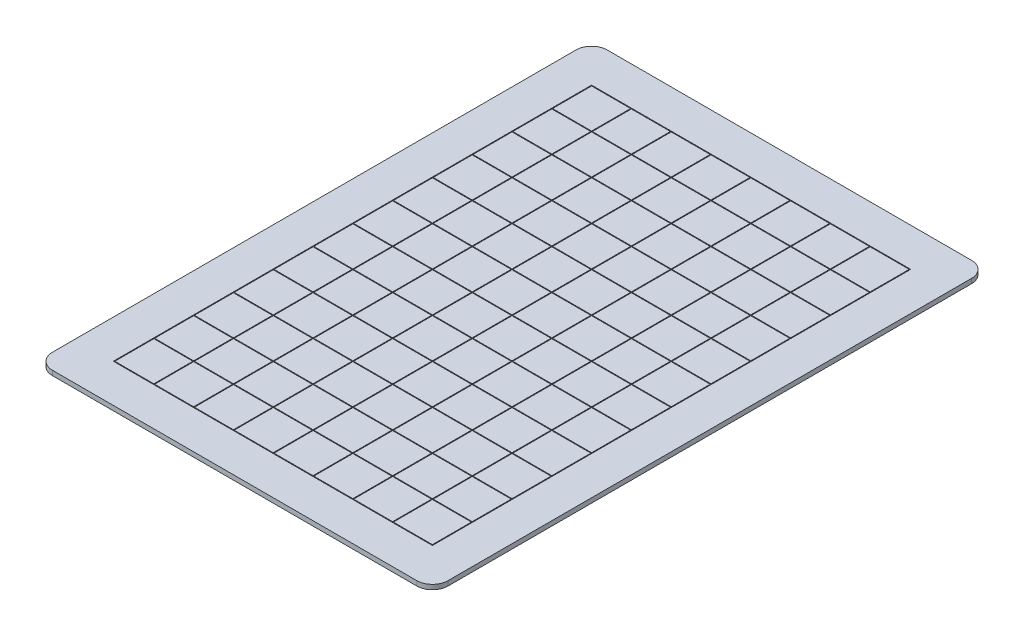
SolidWorks part; units mm, degrees
ref_plane "Front Plane" through (0, 0, 0) normal (0, 0, 1) x (1, 0, 0)
ref_plane "Top Plane" through (0, 0, 0) normal (0, 1, 0) x (1, 0, 0)
ref_plane "Right Plane" through (0, 0, 0) normal (1, 0, 0) x (0, 0, -1)
sketch "Sketch1" plane through (0, 0, 0) normal (0, 1, 0) x (1, 0, 0)
  line L1 (0, 0) -> (253.5, 0)
  line L2 (0, 0) -> (0, 355.5)
  line L3 (0, 355.5) -> (253.5, 355.5)
  line L4 (253.5, 0) -> (253.5, 355.5)
  dimension "D1" = 253.5
  dimension "D2" = 355.5
extrude "Boss-Extrude1" add sketch "Sketch1" along normal blind 3
sketch "Sketch2" plane through (0, 3, 0) normal (0, 1, 0) x (1, 0, 0)
  line L0 (0, 0) -> (253.5, 0) construction
  line L1 (25, 50) -> (50, 50)
  line L2 (25, 50) -> (25, 25)
  line L3 (25, 25) -> (50, 25)
  line L4 (50, 50) -> (50, 25)
  line L5 (0, 355.5) -> (0, 0) construction
  line L6 (50.5, 50) -> (50.5, 25)
  line L7 (50.5, 50) -> (75.5, 50)
  line L8 (75.5, 50) -> (75.5, 25)
  line L9 (50.5, 25) -> (75.5, 25)
  line L10 (76, 50) -> (76, 25)
  line L11 (76, 50) -> (101, 50)
  line L12 (101, 50) -> (101, 25)
  line L13 (76, 25) -> (101, 25)
  line L14 (101.5, 50) -> (101.5, 25)
  line L15 (101.5, 50) -> (126.5, 50)
  line L16 (126.5, 50) -> (126.5, 25)
  line L17 (101.5, 25) -> (126.5, 25)
  line L18 (127, 50) -> (127, 25)
  line L19 (127, 50) -> (152, 50)
  line L20 (152, 50) -> (152, 25)
  line L21 (127, 25) -> (152, 25)
  line L22 (152.5, 50) -> (152.5, 25)
  line L23 (152.5, 50) -> (177.5, 50)
  line L24 (177.5, 50) -> (177.5, 25)
  line L25 (152.5, 25) -> (177.5, 25)
  line L26 (178, 50) -> (178, 25)
  line L27 (178, 50) -> (203, 50)
  line L28 (203, 50) -> (203, 25)
  line L29 (178, 25) -> (203, 25)
  line L30 (203.5, 50) -> (203.5, 25)
  line L31 (203.5, 50) -> (228.5, 50)
  line L32 (228.5, 50) -> (228.5, 25)
  line L33 (203.5, 25) -> (228.5, 25)
  line L34 (50.5, 75.5) -> (50.5, 50.5)
  line L35 (50.5, 75.5) -> (75.5, 75.5)
  line L36 (75.5, 75.5) -> (75.5, 50.5)
  line L37 (50.5, 50.5) -> (75.5, 50.5)
  line L38 (76, 75.5) -> (76, 50.5)
  line L39 (76, 75.5) -> (101, 75.5)
  line L40 (101, 75.5) -> (101, 50.5)
  line L41 (76, 50.5) -> (101, 50.5)
  line L42 (101.5, 75.5) -> (101.5, 50.5)
  line L43 (101.5, 75.5) -> (126.5, 75.5)
  line L44 (126.5, 75.5) -> (126.5, 50.5)
  line L45 (101.5, 50.5) -> (126.5, 50.5)
  line L46 (127, 75.5) -> (127, 50.5)
  line L47 (127, 75.5) -> (152, 75.5)
  line L48 (152, 75.5) -> (152, 50.5)
  line L49 (127, 50.5) -> (152, 50.5)
  line L50 (152.5, 75.5) -> (152.5, 50.5)
  line L51 (152.5, 75.5) -> (177.5, 75.5)
  line L52 (177.5, 75.5) -> (177.5, 50.5)
  line L53 (152.5, 50.5) -> (177.5, 50.5)
  line L54 (178, 75.5) -> (178, 50.5)
  line L55 (178, 75.5) -> (203, 75.5)
  line L56 (203, 75.5) -> (203, 50.5)
  line L57 (178, 50.5) -> (203, 50.5)
  line L58 (203.5, 75.5) -> (203.5, 50.5)
  line L59 (203.5, 75.5) -> (228.5, 75.5)
  line L60 (228.5, 75.5) -> (228.5, 50.5)
  line L61 (203.5, 50.5) -> (228.5, 50.5)
  line L62 (50.5, 101) -> (50.5, 76)
  line L63 (50.5, 101) -> (75.5, 101)
  line L64 (75.5, 101) -> (75.5, 76)
  line L65 (50.5, 76) -> (75.5, 76)
  line L66 (76, 101) -> (76, 76)
  line L67 (76, 101) -> (101, 101)
  line L68 (101, 101) -> (101, 76)
  line L69 (76, 76) -> (101, 76)
  line L70 (101.5, 101) -> (101.5, 76)
  line L71 (101.5, 101) -> (126.5, 101)
  line L72 (126.5, 101) -> (126.5, 76)
  line L73 (101.5, 76) -> (126.5, 76)
  line L74 (127, 101) -> (127, 76)
  line L75 (127, 101) -> (152, 101)
  line L76 (152, 101) -> (152, 76)
  line L77 (127, 76) -> (152, 76)
  line L78 (152.5, 101) -> (152.5, 76)
  line L79 (152.5, 101) -> (177.5, 101)
  line L80 (177.5, 101) -> (177.5, 76)
  line L81 (152.5, 76) -> (177.5, 76)
  line L82 (178, 101) -> (178, 76)
  line L83 (178, 101) -> (203, 101)
  line L84 (203, 101) -> (203, 76)
  line L85 (178, 76) -> (203, 76)
  line L86 (203.5, 101) -> (203.5, 76)
  line L87 (203.5, 101) -> (228.5, 101)
  line L88 (228.5, 101) -> (228.5, 76)
  line L89 (203.5, 76) -> (228.5, 76)
  line L90 (50.5, 126.5) -> (50.5, 101.5)
  line L91 (50.5, 126.5) -> (75.5, 126.5)
  line L92 (75.5, 126.5) -> (75.5, 101.5)
  line L93 (50.5, 101.5) -> (75.5, 101.5)
  line L94 (76, 126.5) -> (76, 101.5)
  line L95 (76, 126.5) -> (101, 126.5)
  line L96 (101, 126.5) -> (101, 101.5)
  line L97 (76, 101.5) -> (101, 101.5)
  line L98 (101.5, 126.5) -> (101.5, 101.5)
  line L99 (101.5, 126.5) -> (126.5, 126.5)
  line L100 (126.5, 126.5) -> (126.5, 101.5)
  line L101 (101.5, 101.5) -> (126.5, 101.5)
  line L102 (127, 126.5) -> (127, 101.5)
  line L103 (127, 126.5) -> (152, 126.5)
  line L104 (152, 126.5) -> (152, 101.5)
  line L105 (127, 101.5) -> (152, 101.5)
  line L106 (152.5, 126.5) -> (152.5, 101.5)
  line L107 (152.5, 126.5) -> (177.5, 126.5)
  line L108 (177.5, 126.5) -> (177.5, 101.5)
  line L109 (152.5, 101.5) -> (177.5, 101.5)
  line L110 (178, 126.5) -> (178, 101.5)
  line L111 (178, 126.5) -> (203, 126.5)
  line L112 (203, 126.5) -> (203, 101.5)
  line L113 (178, 101.5) -> (203, 101.5)
  line L114 (203.5, 126.5) -> (203.5, 101.5)
  line L115 (203.5, 126.5) -> (228.5, 126.5)
  line L116 (228.5, 126.5) -> (228.5, 101.5)
  line L117 (203.5, 101.5) -> (228.5, 101.5)
  line L118 (50.5, 152) -> (50.5, 127)
  line L119 (50.5, 152) -> (75.5, 152)
  line L120 (75.5, 152) -> (75.5, 127)
  line L121 (50.5, 127) -> (75.5, 127)
  line L122 (76, 152) -> (76, 127)
  line L123 (76, 152) -> (101, 152)
  line L124 (101, 152) -> (101, 127)
  line L125 (76, 127) -> (101, 127)
  line L126 (101.5, 152) -> (101.5, 127)
  line L127 (101.5, 152) -> (126.5, 152)
  line L128 (126.5, 152) -> (126.5, 127)
  line L129 (101.5, 127) -> (126.5, 127)
  line L130 (127, 152) -> (127, 127)
  line L131 (127, 152) -> (152, 152)
  line L132 (152, 152) -> (152, 127)
  line L133 (127, 127) -> (152, 127)
  line L134 (152.5, 152) -> (152.5, 127)
  line L135 (152.5, 152) -> (177.5, 152)
  line L136 (177.5, 152) -> (177.5, 127)
  line L137 (152.5, 127) -> (177.5, 127)
  line L138 (178, 152) -> (178, 127)
  line L139 (178, 152) -> (203, 152)
  line L140 (203, 152) -> (203, 127)
  line L141 (178, 127) -> (203, 127)
  line L142 (203.5, 152) -> (203.5, 127)
  line L143 (203.5, 152) -> (228.5, 152)
  line L144 (228.5, 152) -> (228.5, 127)
  line L145 (203.5, 127) -> (228.5, 127)
  line L146 (50.5, 177.5) -> (50.5, 152.5)
  line L147 (50.5, 177.5) -> (75.5, 177.5)
  line L148 (75.5, 177.5) -> (75.5, 152.5)
  line L149 (50.5, 152.5) -> (75.5, 152.5)
  line L150 (76, 177.5) -> (76, 152.5)
  line L151 (76, 177.5) -> (101, 177.5)
  line L152 (101, 177.5) -> (101, 152.5)
  line L153 (76, 152.5) -> (101, 152.5)
  line L154 (101.5, 177.5) -> (101.5, 152.5)
  line L155 (101.5, 177.5) -> (126.5, 177.5)
  line L156 (126.5, 177.5) -> (126.5, 152.5)
  line L157 (101.5, 152.5) -> (126.5, 152.5)
  line L158 (127, 177.5) -> (127, 152.5)
  line L159 (127, 177.5) -> (152, 177.5)
  line L160 (152, 177.5) -> (152, 152.5)
  line L161 (127, 152.5) -> (152, 152.5)
  line L162 (152.5, 177.5) -> (152.5, 152.5)
  line L163 (152.5, 177.5) -> (177.5, 177.5)
  line L164 (177.5, 177.5) -> (177.5, 152.5)
  line L165 (152.5, 152.5) -> (177.5, 152.5)
  line L166 (178, 177.5) -> (178, 152.5)
  line L167 (178, 177.5) -> (203, 177.5)
  line L168 (203, 177.5) -> (203, 152.5)
  line L169 (178, 152.5) -> (203, 152.5)
  line L170 (203.5, 177.5) -> (203.5, 152.5)
  line L171 (203.5, 177.5) -> (228.5, 177.5)
  line L172 (228.5, 177.5) -> (228.5, 152.5)
  line L173 (203.5, 152.5) -> (228.5, 152.5)
  line L174 (50.5, 203) -> (50.5, 178)
  line L175 (50.5, 203) -> (75.5, 203)
  line L176 (75.5, 203) -> (75.5, 178)
  line L177 (50.5, 178) -> (75.5, 178)
  line L178 (76, 203) -> (76, 178)
  line L179 (76, 203) -> (101, 203)
  line L180 (101, 203) -> (101, 178)
  line L181 (76, 178) -> (101, 178)
  line L182 (101.5, 203) -> (101.5, 178)
  line L183 (101.5, 203) -> (126.5, 203)
  line L184 (126.5, 203) -> (126.5, 178)
  line L185 (101.5, 178) -> (126.5, 178)
  line L186 (127, 203) -> (127, 178)
  line L187 (127, 203) -> (152, 203)
  line L188 (152, 203) -> (152, 178)
  line L189 (127, 178) -> (152, 178)
  line L190 (152.5, 203) -> (152.5, 178)
  line L191 (152.5, 203) -> (177.5, 203)
  line L192 (177.5, 203) -> (177.5, 178)
  line L193 (152.5, 178) -> (177.5, 178)
  line L194 (178, 203) -> (178, 178)
  line L195 (178, 203) -> (203, 203)
  line L196 (203, 203) -> (203, 178)
  line L197 (178, 178) -> (203, 178)
  line L198 (203.5, 203) -> (203.5, 178)
  line L199 (203.5, 203) -> (228.5, 203)
  line L200 (228.5, 203) -> (228.5, 178)
  line L201 (203.5, 178) -> (228.5, 178)
  line L202 (50.5, 228.5) -> (50.5, 203.5)
  line L203 (50.5, 228.5) -> (75.5, 228.5)
  line L204 (75.5, 228.5) -> (75.5, 203.5)
  line L205 (50.5, 203.5) -> (75.5, 203.5)
  line L206 (76, 228.5) -> (76, 203.5)
  line L207 (76, 228.5) -> (101, 228.5)
  line L208 (101, 228.5) -> (101, 203.5)
  line L209 (76, 203.5) -> (101, 203.5)
  line L210 (101.5, 228.5) -> (101.5, 203.5)
  line L211 (101.5, 228.5) -> (126.5, 228.5)
  line L212 (126.5, 228.5) -> (126.5, 203.5)
  line L213 (101.5, 203.5) -> (126.5, 203.5)
  line L214 (127, 228.5) -> (127, 203.5)
  line L215 (127, 228.5) -> (152, 228.5)
  line L216 (152, 228.5) -> (152, 203.5)
  line L217 (127, 203.5) -> (152, 203.5)
  line L218 (152.5, 228.5) -> (152.5, 203.5)
  line L219 (152.5, 228.5) -> (177.5, 228.5)
  line L220 (177.5, 228.5) -> (177.5, 203.5)
  line L221 (152.5, 203.5) -> (177.5, 203.5)
  line L222 (178, 228.5) -> (178, 203.5)
  line L223 (178, 228.5) -> (203, 228.5)
  line L224 (203, 228.5) -> (203, 203.5)
  line L225 (178, 203.5) -> (203, 203.5)
  line L226 (203.5, 228.5) -> (203.5, 203.5)
  line L227 (203.5, 228.5) -> (228.5, 228.5)
  line L228 (228.5, 228.5) -> (228.5, 203.5)
  line L229 (203.5, 203.5) -> (228.5, 203.5)
  line L230 (50.5, 254) -> (50.5, 229)
  line L231 (50.5, 254) -> (75.5, 254)
  line L232 (75.5, 254) -> (75.5, 229)
  line L233 (50.5, 229) -> (75.5, 229)
  line L234 (76, 254) -> (76, 229)
  line L235 (76, 254) -> (101, 254)
  line L236 (101, 254) -> (101, 229)
  line L237 (76, 229) -> (101, 229)
  line L238 (101.5, 254) -> (101.5, 229)
  line L239 (101.5, 254) -> (126.5, 254)
  line L240 (126.5, 254) -> (126.5, 229)
  line L241 (101.5, 229) -> (126.5, 229)
  line L242 (127, 254) -> (127, 229)
  line L243 (127, 254) -> (152, 254)
  line L244 (152, 254) -> (152, 229)
  line L245 (127, 229) -> (152, 229)
  line L246 (152.5, 254) -> (152.5, 229)
  line L247 (152.5, 254) -> (177.5, 254)
  line L248 (177.5, 254) -> (177.5, 229)
  line L249 (152.5, 229) -> (177.5, 229)
  line L250 (178, 254) -> (178, 229)
  line L251 (178, 254) -> (203, 254)
  line L252 (203, 254) -> (203, 229)
  line L253 (178, 229) -> (203, 229)
  line L254 (203.5, 254) -> (203.5, 229)
  line L255 (203.5, 254) -> (228.5, 254)
  line L256 (228.5, 254) -> (228.5, 229)
  line L257 (203.5, 229) -> (228.5, 229)
  line L258 (50.5, 279.5) -> (50.5, 254.5)
  line L259 (50.5, 279.5) -> (75.5, 279.5)
  line L260 (75.5, 279.5) -> (75.5, 254.5)
  line L261 (50.5, 254.5) -> (75.5, 254.5)
  line L262 (76, 279.5) -> (76, 254.5)
  line L263 (76, 279.5) -> (101, 279.5)
  line L264 (101, 279.5) -> (101, 254.5)
  line L265 (76, 254.5) -> (101, 254.5)
  line L266 (101.5, 279.5) -> (101.5, 254.5)
  line L267 (101.5, 279.5) -> (126.5, 279.5)
  line L268 (126.5, 279.5) -> (126.5, 254.5)
  line L269 (101.5, 254.5) -> (126.5, 254.5)
  line L270 (127, 279.5) -> (127, 254.5)
  line L271 (127, 279.5) -> (152, 279.5)
  line L272 (152, 279.5) -> (152, 254.5)
  line L273 (127, 254.5) -> (152, 254.5)
  line L274 (152.5, 279.5) -> (152.5, 254.5)
  line L275 (152.5, 279.5) -> (177.5, 279.5)
  line L276 (177.5, 279.5) -> (177.5, 254.5)
  line L277 (152.5, 254.5) -> (177.5, 254.5)
  line L278 (178, 279.5) -> (178, 254.5)
  line L279 (178, 279.5) -> (203, 279.5)
  line L280 (203, 279.5) -> (203, 254.5)
  line L281 (178, 254.5) -> (203, 254.5)
  line L282 (203.5, 279.5) -> (203.5, 254.5)
  line L283 (203.5, 279.5) -> (228.5, 279.5)
  line L284 (228.5, 279.5) -> (228.5, 254.5)
  line L285 (203.5, 254.5) -> (228.5, 254.5)
  line L286 (50.5, 305) -> (50.5, 280)
  line L287 (50.5, 305) -> (75.5, 305)
  line L288 (75.5, 305) -> (75.5, 280)
  line L289 (50.5, 280) -> (75.5, 280)
  line L290 (76, 305) -> (76, 280)
  line L291 (76, 305) -> (101, 305)
  line L292 (101, 305) -> (101, 280)
  line L293 (76, 280) -> (101, 280)
  line L294 (101.5, 305) -> (101.5, 280)
  line L295 (101.5, 305) -> (126.5, 305)
  line L296 (126.5, 305) -> (126.5, 280)
  line L297 (101.5, 280) -> (126.5, 280)
  line L298 (127, 305) -> (127, 280)
  line L299 (127, 305) -> (152, 305)
  line L300 (152, 305) -> (152, 280)
  line L301 (127, 280) -> (152, 280)
  line L302 (152.5, 305) -> (152.5, 280)
  line L303 (152.5, 305) -> (177.5, 305)
  line L304 (177.5, 305) -> (177.5, 280)
  line L305 (152.5, 280) -> (177.5, 280)
  line L306 (178, 305) -> (178, 280)
  line L307 (178, 305) -> (203, 305)
  line L308 (203, 305) -> (203, 280)
  line L309 (178, 280) -> (203, 280)
  line L310 (203.5, 305) -> (203.5, 280)
  line L311 (203.5, 305) -> (228.5, 305)
  line L312 (228.5, 305) -> (228.5, 280)
  line L313 (203.5, 280) -> (228.5, 280)
  line L314 (50.5, 330.5) -> (50.5, 305.5)
  line L315 (50.5, 330.5) -> (75.5, 330.5)
  line L316 (75.5, 330.5) -> (75.5, 305.5)
  line L317 (50.5, 305.5) -> (75.5, 305.5)
  line L318 (76, 330.5) -> (76, 305.5)
  line L319 (76, 330.5) -> (101, 330.5)
  line L320 (101, 330.5) -> (101, 305.5)
  line L321 (76, 305.5) -> (101, 305.5)
  line L322 (101.5, 330.5) -> (101.5, 305.5)
  line L323 (101.5, 330.5) -> (126.5, 330.5)
  line L324 (126.5, 330.5) -> (126.5, 305.5)
  line L325 (101.5, 305.5) -> (126.5, 305.5)
  line L326 (127, 330.5) -> (127, 305.5)
  line L327 (127, 330.5) -> (152, 330.5)
  line L328 (152, 330.5) -> (152, 305.5)
  line L329 (127, 305.5) -> (152, 305.5)
  line L330 (152.5, 330.5) -> (152.5, 305.5)
  line L331 (152.5, 330.5) -> (177.5, 330.5)
  line L332 (177.5, 330.5) -> (177.5, 305.5)
  line L333 (152.5, 305.5) -> (177.5, 305.5)
  line L334 (178, 330.5) -> (178, 305.5)
  line L335 (178, 330.5) -> (203, 330.5)
  line L336 (203, 330.5) -> (203, 305.5)
  line L337 (178, 305.5) -> (203, 305.5)
  line L338 (203.5, 330.5) -> (203.5, 305.5)
  line L339 (203.5, 330.5) -> (228.5, 330.5)
  line L340 (228.5, 330.5) -> (228.5, 305.5)
  line L341 (203.5, 305.5) -> (228.5, 305.5)
  line L342 (25, 75.5) -> (25, 50.5)
  line L343 (25, 75.5) -> (50, 75.5)
  line L344 (50, 75.5) -> (50, 50.5)
  line L345 (25, 50.5) -> (50, 50.5)
  line L346 (25, 101) -> (25, 76)
  line L347 (25, 101) -> (50, 101)
  line L348 (50, 101) -> (50, 76)
  line L349 (25, 76) -> (50, 76)
  line L350 (25, 126.5) -> (25, 101.5)
  line L351 (25, 126.5) -> (50, 126.5)
  line L352 (50, 126.5) -> (50, 101.5)
  line L353 (25, 101.5) -> (50, 101.5)
  line L354 (25, 152) -> (25, 127)
  line L355 (25, 152) -> (50, 152)
  line L356 (50, 152) -> (50, 127)
  line L357 (25, 127) -> (50, 127)
  line L358 (25, 177.5) -> (25, 152.5)
  line L359 (25, 177.5) -> (50, 177.5)
  line L360 (50, 177.5) -> (50, 152.5)
  line L361 (25, 152.5) -> (50, 152.5)
  line L362 (25, 203) -> (25, 178)
  line L363 (25, 203) -> (50, 203)
  line L364 (50, 203) -> (50, 178)
  line L365 (25, 178) -> (50, 178)
  line L366 (25, 228.5) -> (25, 203.5)
  line L367 (25, 228.5) -> (50, 228.5)
  line L368 (50, 228.5) -> (50, 203.5)
  line L369 (25, 203.5) -> (50, 203.5)
  line L370 (25, 254) -> (25, 229)
  line L371 (25, 254) -> (50, 254)
  line L372 (50, 254) -> (50, 229)
  line L373 (25, 229) -> (50, 229)
  line L374 (25, 279.5) -> (25, 254.5)
  line L375 (25, 279.5) -> (50, 279.5)
  line L376 (50, 279.5) -> (50, 254.5)
  line L377 (25, 254.5) -> (50, 254.5)
  line L378 (25, 305) -> (25, 280)
  line L379 (25, 305) -> (50, 305)
  line L380 (50, 305) -> (50, 280)
  line L381 (25, 280) -> (50, 280)
  line L382 (25, 330.5) -> (25, 305.5)
  line L383 (25, 330.5) -> (50, 330.5)
  line L384 (50, 330.5) -> (50, 305.5)
  line L385 (25, 305.5) -> (50, 305.5)
  line L387 (24.5, 331) -> (229, 331)
  line L388 (24.5, 331) -> (24.5, 24.5)
  line L389 (24.5, 24.5) -> (229, 24.5)
  line L390 (229, 331) -> (229, 24.5)
  dimension "D1" = 25
  dimension "D2" = 25
  dimension "D3" = 25
  dimension "D4" = 25
  dimension "D7" = 0.5
  dimension "D8" = 0.5
  dimension "D9" = 0.5
  dimension "D10" = 0.5
  dimension "D11" = 0.5
  dimension "D5" = 8
  dimension "D6" = 12
extrude "Cut-Extrude1" cut sketch "Sketch2" against normal blind 0.5
sketch "Sketch4" plane through (0, 0, 0) normal (0, -1, 0) x (1, 0, 0)
  line L0 (0, -355.5) -> (0, 0) construction
  line L1 (0, 0) -> (253.5, 0) construction
  line L2 (253.5, -355.5) -> (0, -355.5) construction
  line L3 (0, 0) -> (253.5, 0)
  line L4 (253.5, -355.5) -> (0, -355.5)
  line L5 (126.75, -355.5) -> (126.75, 0)
  line L6 (253.5, 0) -> (253.5, -355.5) construction
  line L7 (0, -355.5) -> (0, 0) construction
  line L8 (253.5, 0) -> (253.5, -355.5)
  line L9 (0, -355.5) -> (0, 0)
  line L10 (0, -177.75) -> (253.5, -177.75)
  circle A0 centre (6, -6) radius 1.6
  circle A1 centre (6, -91.875) radius 1.6
  circle A2 centre (6, -177.75) radius 1.6
  circle A3 centre (6, -263.625) radius 1.6
  circle A4 centre (6, -349.5) radius 1.6
  circle A5 centre (247.5, -6) radius 1.6
  circle A6 centre (247.5, -91.875) radius 1.6
  circle A7 centre (247.5, -177.75) radius 1.6
  circle A8 centre (247.5, -263.625) radius 1.6
  circle A10 centre (86.5, -349.5) radius 1.6
  circle A11 centre (167, -349.5) radius 1.6
  circle A12 centre (247.5, -349.5) radius 1.6
  circle A13 centre (167, -6) radius 1.6
  circle A14 centre (86.5, -6) radius 1.6
  dimension "D1" = 3.2
  dimension "D2" = 6
  dimension "D3" = 6
  dimension "D5" = 6
  dimension "D7" = 6
  dimension "D4" = 5
  dimension "D6" = 4
extrude "Cut-Extrude2" cut sketch "Sketch4" against normal blind 1.2 contours A14 | A0 | A13 | A5 | A6 | A7 L10 | A7 L10 | A8 | A12 | A11 | A10 | A4 | A3 | L10 A2 | L10 A2 | A1 region at (6, 0, -177.0709) region at (6, 0, -178.4291) region at (247.5, 0, -177.0709) region at (247.5, 0, -178.4291) region at (6, 0, -6) region at (6, 0, -91.875) region at (6, 0, -263.625) region at (6, 0, -349.5) region at (247.5, 0, -6) region at (247.5, 0, -91.875) region at (247.5, 0, -263.625) region at (86.5, 0, -349.5) region at (167, 0, -349.5) region at (247.5, 0, -349.5) region at (167, 0, -6) region at (86.5, 0, -6)
fillet "Fillet1" radius 10 4 edges at (253.5, 1.5, 0) (0, 1.5, 0) (0, 1.5, -355.5) (253.5, 1.5, -355.5)
sketch "Sketch5" plane through (0, 0, 0) normal (0, -1, 0) x (1, 0, 0)
  line L1 (218.5, -265) -> (213.5, -265)
  line L2 (218.5, -265) -> (218.5, -269)
  line L3 (218.5, -269) -> (213.5, -269)
  line L4 (213.5, -265) -> (213.5, -269)
  line L6 (216, -265) -> (216, -269)
  line L9 (203.5, -279.5) -> (203.5, -254.5) construction
  line L10 (228.5, -279.5) -> (203.5, -279.5) construction
  line L11 (216, -271) -> (216, -275.38)
  line L12 (218.5, -271) -> (213.5, -271)
  line L13 (218.5, -271) -> (218.5, -275.38)
  line L14 (218.5, -275.38) -> (213.5, -275.38)
  line L15 (213.5, -271) -> (213.5, -275.38)
  line L16 (193, -265) -> (193, -269)
  line L17 (193, -265) -> (188, -265)
  line L18 (188, -265) -> (188, -269)
  line L19 (193, -269) -> (188, -269)
  line L20 (193, -271) -> (193, -275.38)
  line L21 (193, -271) -> (188, -271)
  line L22 (188, -271) -> (188, -275.38)
  line L23 (193, -275.38) -> (188, -275.38)
  line L24 (167.5, -265) -> (167.5, -269)
  line L25 (167.5, -265) -> (162.5, -265)
  line L26 (162.5, -265) -> (162.5, -269)
  line L27 (167.5, -269) -> (162.5, -269)
  line L28 (167.5, -271) -> (167.5, -275.38)
  line L29 (167.5, -271) -> (162.5, -271)
  line L30 (162.5, -271) -> (162.5, -275.38)
  line L31 (167.5, -275.38) -> (162.5, -275.38)
  line L32 (142, -265) -> (142, -269)
  line L33 (142, -265) -> (137, -265)
  line L34 (137, -265) -> (137, -269)
  line L35 (142, -269) -> (137, -269)
  line L36 (142, -271) -> (142, -275.38)
  line L37 (142, -271) -> (137, -271)
  line L38 (137, -271) -> (137, -275.38)
  line L39 (142, -275.38) -> (137, -275.38)
  line L40 (116.5, -265) -> (116.5, -269)
  line L41 (116.5, -265) -> (111.5, -265)
  line L42 (111.5, -265) -> (111.5, -269)
  line L43 (116.5, -269) -> (111.5, -269)
  line L44 (116.5, -271) -> (116.5, -275.38)
  line L45 (116.5, -271) -> (111.5, -271)
  line L46 (111.5, -271) -> (111.5, -275.38)
  line L47 (116.5, -275.38) -> (111.5, -275.38)
  line L48 (91, -265) -> (91, -269)
  line L49 (91, -265) -> (86, -265)
  line L50 (86, -265) -> (86, -269)
  line L51 (91, -269) -> (86, -269)
  line L52 (91, -271) -> (91, -275.38)
  line L53 (91, -271) -> (86, -271)
  line L54 (86, -271) -> (86, -275.38)
  line L55 (91, -275.38) -> (86, -275.38)
  line L56 (65.5, -265) -> (65.5, -269)
  line L57 (65.5, -265) -> (60.5, -265)
  line L58 (60.5, -265) -> (60.5, -269)
  line L59 (65.5, -269) -> (60.5, -269)
  line L60 (65.5, -271) -> (65.5, -275.38)
  line L61 (65.5, -271) -> (60.5, -271)
  line L62 (60.5, -271) -> (60.5, -275.38)
  line L63 (65.5, -275.38) -> (60.5, -275.38)
  line L64 (40, -265) -> (40, -269)
  line L65 (40, -265) -> (35, -265)
  line L66 (35, -265) -> (35, -269)
  line L67 (40, -269) -> (35, -269)
  line L68 (40, -271) -> (40, -275.38)
  line L69 (40, -271) -> (35, -271)
  line L70 (35, -271) -> (35, -275.38)
  line L71 (40, -275.38) -> (35, -275.38)
  line L72 (193, -239.5) -> (193, -243.5)
  line L73 (193, -239.5) -> (188, -239.5)
  line L74 (188, -239.5) -> (188, -243.5)
  line L75 (193, -243.5) -> (188, -243.5)
  line L76 (193, -245.5) -> (193, -249.88)
  line L77 (193, -245.5) -> (188, -245.5)
  line L78 (188, -245.5) -> (188, -249.88)
  line L79 (193, -249.88) -> (188, -249.88)
  line L80 (167.5, -239.5) -> (167.5, -243.5)
  line L81 (167.5, -239.5) -> (162.5, -239.5)
  line L82 (162.5, -239.5) -> (162.5, -243.5)
  line L83 (167.5, -243.5) -> (162.5, -243.5)
  line L84 (167.5, -245.5) -> (167.5, -249.88)
  line L85 (167.5, -245.5) -> (162.5, -245.5)
  line L86 (162.5, -245.5) -> (162.5, -249.88)
  line L87 (167.5, -249.88) -> (162.5, -249.88)
  line L88 (142, -239.5) -> (142, -243.5)
  line L89 (142, -239.5) -> (137, -239.5)
  line L90 (137, -239.5) -> (137, -243.5)
  line L91 (142, -243.5) -> (137, -243.5)
  line L92 (142, -245.5) -> (142, -249.88)
  line L93 (142, -245.5) -> (137, -245.5)
  line L94 (137, -245.5) -> (137, -249.88)
  line L95 (142, -249.88) -> (137, -249.88)
  line L96 (116.5, -239.5) -> (116.5, -243.5)
  line L97 (116.5, -239.5) -> (111.5, -239.5)
  line L98 (111.5, -239.5) -> (111.5, -243.5)
  line L99 (116.5, -243.5) -> (111.5, -243.5)
  line L100 (116.5, -245.5) -> (116.5, -249.88)
  line L101 (116.5, -245.5) -> (111.5, -245.5)
  line L102 (111.5, -245.5) -> (111.5, -249.88)
  line L103 (116.5, -249.88) -> (111.5, -249.88)
  line L104 (91, -239.5) -> (91, -243.5)
  line L105 (91, -239.5) -> (86, -239.5)
  line L106 (86, -239.5) -> (86, -243.5)
  line L107 (91, -243.5) -> (86, -243.5)
  line L108 (91, -245.5) -> (91, -249.88)
  line L109 (91, -245.5) -> (86, -245.5)
  line L110 (86, -245.5) -> (86, -249.88)
  line L111 (91, -249.88) -> (86, -249.88)
  line L112 (65.5, -239.5) -> (65.5, -243.5)
  line L113 (65.5, -239.5) -> (60.5, -239.5)
  line L114 (60.5, -239.5) -> (60.5, -243.5)
  line L115 (65.5, -243.5) -> (60.5, -243.5)
  line L116 (65.5, -245.5) -> (65.5, -249.88)
  line L117 (65.5, -245.5) -> (60.5, -245.5)
  line L118 (60.5, -245.5) -> (60.5, -249.88)
  line L119 (65.5, -249.88) -> (60.5, -249.88)
  line L120 (40, -239.5) -> (40, -243.5)
  line L121 (40, -239.5) -> (35, -239.5)
  line L122 (35, -239.5) -> (35, -243.5)
  line L123 (40, -243.5) -> (35, -243.5)
  line L124 (40, -245.5) -> (40, -249.88)
  line L125 (40, -245.5) -> (35, -245.5)
  line L126 (35, -245.5) -> (35, -249.88)
  line L127 (40, -249.88) -> (35, -249.88)
  line L128 (193, -214) -> (193, -218)
  line L129 (193, -214) -> (188, -214)
  line L130 (188, -214) -> (188, -218)
  line L131 (193, -218) -> (188, -218)
  line L132 (193, -220) -> (193, -224.38)
  line L133 (193, -220) -> (188, -220)
  line L134 (188, -220) -> (188, -224.38)
  line L135 (193, -224.38) -> (188, -224.38)
  line L136 (167.5, -214) -> (167.5, -218)
  line L137 (167.5, -214) -> (162.5, -214)
  line L138 (162.5, -214) -> (162.5, -218)
  line L139 (167.5, -218) -> (162.5, -218)
  line L140 (167.5, -220) -> (167.5, -224.38)
  line L141 (167.5, -220) -> (162.5, -220)
  line L142 (162.5, -220) -> (162.5, -224.38)
  line L143 (167.5, -224.38) -> (162.5, -224.38)
  line L144 (142, -214) -> (142, -218)
  line L145 (142, -214) -> (137, -214)
  line L146 (137, -214) -> (137, -218)
  line L147 (142, -218) -> (137, -218)
  line L148 (142, -220) -> (142, -224.38)
  line L149 (142, -220) -> (137, -220)
  line L150 (137, -220) -> (137, -224.38)
  line L151 (142, -224.38) -> (137, -224.38)
  line L152 (116.5, -214) -> (116.5, -218)
  line L153 (116.5, -214) -> (111.5, -214)
  line L154 (111.5, -214) -> (111.5, -218)
  line L155 (116.5, -218) -> (111.5, -218)
  line L156 (116.5, -220) -> (116.5, -224.38)
  line L157 (116.5, -220) -> (111.5, -220)
  line L158 (111.5, -220) -> (111.5, -224.38)
  line L159 (116.5, -224.38) -> (111.5, -224.38)
  line L160 (91, -214) -> (91, -218)
  line L161 (91, -214) -> (86, -214)
  line L162 (86, -214) -> (86, -218)
  line L163 (91, -218) -> (86, -218)
  line L164 (91, -220) -> (91, -224.38)
  line L165 (91, -220) -> (86, -220)
  line L166 (86, -220) -> (86, -224.38)
  line L167 (91, -224.38) -> (86, -224.38)
  line L168 (65.5, -214) -> (65.5, -218)
  line L169 (65.5, -214) -> (60.5, -214)
  line L170 (60.5, -214) -> (60.5, -218)
  line L171 (65.5, -218) -> (60.5, -218)
  line L172 (65.5, -220) -> (65.5, -224.38)
  line L173 (65.5, -220) -> (60.5, -220)
  line L174 (60.5, -220) -> (60.5, -224.38)
  line L175 (65.5, -224.38) -> (60.5, -224.38)
  line L176 (40, -214) -> (40, -218)
  line L177 (40, -214) -> (35, -214)
  line L178 (35, -214) -> (35, -218)
  line L179 (40, -218) -> (35, -218)
  line L180 (40, -220) -> (40, -224.38)
  line L181 (40, -220) -> (35, -220)
  line L182 (35, -220) -> (35, -224.38)
  line L183 (40, -224.38) -> (35, -224.38)
  line L184 (193, -188.5) -> (193, -192.5)
  line L185 (193, -188.5) -> (188, -188.5)
  line L186 (188, -188.5) -> (188, -192.5)
  line L187 (193, -192.5) -> (188, -192.5)
  line L188 (193, -194.5) -> (193, -198.88)
  line L189 (193, -194.5) -> (188, -194.5)
  line L190 (188, -194.5) -> (188, -198.88)
  line L191 (193, -198.88) -> (188, -198.88)
  line L192 (167.5, -188.5) -> (167.5, -192.5)
  line L193 (167.5, -188.5) -> (162.5, -188.5)
  line L194 (162.5, -188.5) -> (162.5, -192.5)
  line L195 (167.5, -192.5) -> (162.5, -192.5)
  line L196 (167.5, -194.5) -> (167.5, -198.88)
  line L197 (167.5, -194.5) -> (162.5, -194.5)
  line L198 (162.5, -194.5) -> (162.5, -198.88)
  line L199 (167.5, -198.88) -> (162.5, -198.88)
  line L200 (142, -188.5) -> (142, -192.5)
  line L201 (142, -188.5) -> (137, -188.5)
  line L202 (137, -188.5) -> (137, -192.5)
  line L203 (142, -192.5) -> (137, -192.5)
  line L204 (142, -194.5) -> (142, -198.88)
  line L205 (142, -194.5) -> (137, -194.5)
  line L206 (137, -194.5) -> (137, -198.88)
  line L207 (142, -198.88) -> (137, -198.88)
  line L208 (116.5, -188.5) -> (116.5, -192.5)
  line L209 (116.5, -188.5) -> (111.5, -188.5)
  line L210 (111.5, -188.5) -> (111.5, -192.5)
  line L211 (116.5, -192.5) -> (111.5, -192.5)
  line L212 (116.5, -194.5) -> (116.5, -198.88)
  line L213 (116.5, -194.5) -> (111.5, -194.5)
  line L214 (111.5, -194.5) -> (111.5, -198.88)
  line L215 (116.5, -198.88) -> (111.5, -198.88)
  line L216 (91, -188.5) -> (91, -192.5)
  line L217 (91, -188.5) -> (86, -188.5)
  line L218 (86, -188.5) -> (86, -192.5)
  line L219 (91, -192.5) -> (86, -192.5)
  line L220 (91, -194.5) -> (91, -198.88)
  line L221 (91, -194.5) -> (86, -194.5)
  line L222 (86, -194.5) -> (86, -198.88)
  line L223 (91, -198.88) -> (86, -198.88)
  line L224 (65.5, -188.5) -> (65.5, -192.5)
  line L225 (65.5, -188.5) -> (60.5, -188.5)
  line L226 (60.5, -188.5) -> (60.5, -192.5)
  line L227 (65.5, -192.5) -> (60.5, -192.5)
  line L228 (65.5, -194.5) -> (65.5, -198.88)
  line L229 (65.5, -194.5) -> (60.5, -194.5)
  line L230 (60.5, -194.5) -> (60.5, -198.88)
  line L231 (65.5, -198.88) -> (60.5, -198.88)
  line L232 (40, -188.5) -> (40, -192.5)
  line L233 (40, -188.5) -> (35, -188.5)
  line L234 (35, -188.5) -> (35, -192.5)
  line L235 (40, -192.5) -> (35, -192.5)
  line L236 (40, -194.5) -> (40, -198.88)
  line L237 (40, -194.5) -> (35, -194.5)
  line L238 (35, -194.5) -> (35, -198.88)
  line L239 (40, -198.88) -> (35, -198.88)
  line L240 (193, -163) -> (193, -167)
  line L241 (193, -163) -> (188, -163)
  line L242 (188, -163) -> (188, -167)
  line L243 (193, -167) -> (188, -167)
  line L244 (193, -169) -> (193, -173.38)
  line L245 (193, -169) -> (188, -169)
  line L246 (188, -169) -> (188, -173.38)
  line L247 (193, -173.38) -> (188, -173.38)
  line L248 (167.5, -163) -> (167.5, -167)
  line L249 (167.5, -163) -> (162.5, -163)
  line L250 (162.5, -163) -> (162.5, -167)
  line L251 (167.5, -167) -> (162.5, -167)
  line L252 (167.5, -169) -> (167.5, -173.38)
  line L253 (167.5, -169) -> (162.5, -169)
  line L254 (162.5, -169) -> (162.5, -173.38)
  line L255 (167.5, -173.38) -> (162.5, -173.38)
  line L256 (142, -163) -> (142, -167)
  line L257 (142, -163) -> (137, -163)
  line L258 (137, -163) -> (137, -167)
  line L259 (142, -167) -> (137, -167)
  line L260 (142, -169) -> (142, -173.38)
  line L261 (142, -169) -> (137, -169)
  line L262 (137, -169) -> (137, -173.38)
  line L263 (142, -173.38) -> (137, -173.38)
  line L264 (116.5, -163) -> (116.5, -167)
  line L265 (116.5, -163) -> (111.5, -163)
  line L266 (111.5, -163) -> (111.5, -167)
  line L267 (116.5, -167) -> (111.5, -167)
  line L268 (116.5, -169) -> (116.5, -173.38)
  line L269 (116.5, -169) -> (111.5, -169)
  line L270 (111.5, -169) -> (111.5, -173.38)
  line L271 (116.5, -173.38) -> (111.5, -173.38)
  line L272 (91, -163) -> (91, -167)
  line L273 (91, -163) -> (86, -163)
  line L274 (86, -163) -> (86, -167)
  line L275 (91, -167) -> (86, -167)
  line L276 (91, -169) -> (91, -173.38)
  line L277 (91, -169) -> (86, -169)
  line L278 (86, -169) -> (86, -173.38)
  line L279 (91, -173.38) -> (86, -173.38)
  line L280 (65.5, -163) -> (65.5, -167)
  line L281 (65.5, -163) -> (60.5, -163)
  line L282 (60.5, -163) -> (60.5, -167)
  line L283 (65.5, -167) -> (60.5, -167)
  line L284 (65.5, -169) -> (65.5, -173.38)
  line L285 (65.5, -169) -> (60.5, -169)
  line L286 (60.5, -169) -> (60.5, -173.38)
  line L287 (65.5, -173.38) -> (60.5, -173.38)
  line L288 (40, -163) -> (40, -167)
  line L289 (40, -163) -> (35, -163)
  line L290 (35, -163) -> (35, -167)
  line L291 (40, -167) -> (35, -167)
  line L292 (40, -169) -> (40, -173.38)
  line L293 (40, -169) -> (35, -169)
  line L294 (35, -169) -> (35, -173.38)
  line L295 (40, -173.38) -> (35, -173.38)
  line L296 (193, -137.5) -> (193, -141.5)
  line L297 (193, -137.5) -> (188, -137.5)
  line L298 (188, -137.5) -> (188, -141.5)
  line L299 (193, -141.5) -> (188, -141.5)
  line L300 (193, -143.5) -> (193, -147.88)
  line L301 (193, -143.5) -> (188, -143.5)
  line L302 (188, -143.5) -> (188, -147.88)
  line L303 (193, -147.88) -> (188, -147.88)
  line L304 (167.5, -137.5) -> (167.5, -141.5)
  line L305 (167.5, -137.5) -> (162.5, -137.5)
  line L306 (162.5, -137.5) -> (162.5, -141.5)
  line L307 (167.5, -141.5) -> (162.5, -141.5)
  line L308 (167.5, -143.5) -> (167.5, -147.88)
  line L309 (167.5, -143.5) -> (162.5, -143.5)
  line L310 (162.5, -143.5) -> (162.5, -147.88)
  line L311 (167.5, -147.88) -> (162.5, -147.88)
  line L312 (142, -137.5) -> (142, -141.5)
  line L313 (142, -137.5) -> (137, -137.5)
  line L314 (137, -137.5) -> (137, -141.5)
  line L315 (142, -141.5) -> (137, -141.5)
  line L316 (142, -143.5) -> (142, -147.88)
  line L317 (142, -143.5) -> (137, -143.5)
  line L318 (137, -143.5) -> (137, -147.88)
  line L319 (142, -147.88) -> (137, -147.88)
  line L320 (116.5, -137.5) -> (116.5, -141.5)
  line L321 (116.5, -137.5) -> (111.5, -137.5)
  line L322 (111.5, -137.5) -> (111.5, -141.5)
  line L323 (116.5, -141.5) -> (111.5, -141.5)
  line L324 (116.5, -143.5) -> (116.5, -147.88)
  line L325 (116.5, -143.5) -> (111.5, -143.5)
  line L326 (111.5, -143.5) -> (111.5, -147.88)
  line L327 (116.5, -147.88) -> (111.5, -147.88)
  line L328 (91, -137.5) -> (91, -141.5)
  line L329 (91, -137.5) -> (86, -137.5)
  line L330 (86, -137.5) -> (86, -141.5)
  line L331 (91, -141.5) -> (86, -141.5)
  line L332 (91, -143.5) -> (91, -147.88)
  line L333 (91, -143.5) -> (86, -143.5)
  line L334 (86, -143.5) -> (86, -147.88)
  line L335 (91, -147.88) -> (86, -147.88)
  line L336 (65.5, -137.5) -> (65.5, -141.5)
  line L337 (65.5, -137.5) -> (60.5, -137.5)
  line L338 (60.5, -137.5) -> (60.5, -141.5)
  line L339 (65.5, -141.5) -> (60.5, -141.5)
  line L340 (65.5, -143.5) -> (65.5, -147.88)
  line L341 (65.5, -143.5) -> (60.5, -143.5)
  line L342 (60.5, -143.5) -> (60.5, -147.88)
  line L343 (65.5, -147.88) -> (60.5, -147.88)
  line L344 (40, -137.5) -> (40, -141.5)
  line L345 (40, -137.5) -> (35, -137.5)
  line L346 (35, -137.5) -> (35, -141.5)
  line L347 (40, -141.5) -> (35, -141.5)
  line L348 (40, -143.5) -> (40, -147.88)
  line L349 (40, -143.5) -> (35, -143.5)
  line L350 (35, -143.5) -> (35, -147.88)
  line L351 (40, -147.88) -> (35, -147.88)
  line L352 (193, -112) -> (193, -116)
  line L353 (193, -112) -> (188, -112)
  line L354 (188, -112) -> (188, -116)
  line L355 (193, -116) -> (188, -116)
  line L356 (193, -118) -> (193, -122.38)
  line L357 (193, -118) -> (188, -118)
  line L358 (188, -118) -> (188, -122.38)
  line L359 (193, -122.38) -> (188, -122.38)
  line L360 (167.5, -112) -> (167.5, -116)
  line L361 (167.5, -112) -> (162.5, -112)
  line L362 (162.5, -112) -> (162.5, -116)
  line L363 (167.5, -116) -> (162.5, -116)
  line L364 (167.5, -118) -> (167.5, -122.38)
  line L365 (167.5, -118) -> (162.5, -118)
  line L366 (162.5, -118) -> (162.5, -122.38)
  line L367 (167.5, -122.38) -> (162.5, -122.38)
  line L368 (142, -112) -> (142, -116)
  line L369 (142, -112) -> (137, -112)
  line L370 (137, -112) -> (137, -116)
  line L371 (142, -116) -> (137, -116)
  line L372 (142, -118) -> (142, -122.38)
  line L373 (142, -118) -> (137, -118)
  line L374 (137, -118) -> (137, -122.38)
  line L375 (142, -122.38) -> (137, -122.38)
  line L376 (116.5, -112) -> (116.5, -116)
  line L377 (116.5, -112) -> (111.5, -112)
  line L378 (111.5, -112) -> (111.5, -116)
  line L379 (116.5, -116) -> (111.5, -116)
  line L380 (116.5, -118) -> (116.5, -122.38)
  line L381 (116.5, -118) -> (111.5, -118)
  line L382 (111.5, -118) -> (111.5, -122.38)
  line L383 (116.5, -122.38) -> (111.5, -122.38)
  line L384 (91, -112) -> (91, -116)
  line L385 (91, -112) -> (86, -112)
  line L386 (86, -112) -> (86, -116)
  line L387 (91, -116) -> (86, -116)
  line L388 (91, -118) -> (91, -122.38)
  line L389 (91, -118) -> (86, -118)
  line L390 (86, -118) -> (86, -122.38)
  line L391 (91, -122.38) -> (86, -122.38)
  line L392 (65.5, -112) -> (65.5, -116)
  line L393 (65.5, -112) -> (60.5, -112)
  line L394 (60.5, -112) -> (60.5, -116)
  line L395 (65.5, -116) -> (60.5, -116)
  line L396 (65.5, -118) -> (65.5, -122.38)
  line L397 (65.5, -118) -> (60.5, -118)
  line L398 (60.5, -118) -> (60.5, -122.38)
  line L399 (65.5, -122.38) -> (60.5, -122.38)
  line L400 (40, -112) -> (40, -116)
  line L401 (40, -112) -> (35, -112)
  line L402 (35, -112) -> (35, -116)
  line L403 (40, -116) -> (35, -116)
  line L404 (40, -118) -> (40, -122.38)
  line L405 (40, -118) -> (35, -118)
  line L406 (35, -118) -> (35, -122.38)
  line L407 (40, -122.38) -> (35, -122.38)
  line L408 (193, -86.5) -> (193, -90.5)
  line L409 (193, -86.5) -> (188, -86.5)
  line L410 (188, -86.5) -> (188, -90.5)
  line L411 (193, -90.5) -> (188, -90.5)
  line L412 (193, -92.5) -> (193, -96.88)
  line L413 (193, -92.5) -> (188, -92.5)
  line L414 (188, -92.5) -> (188, -96.88)
  line L415 (193, -96.88) -> (188, -96.88)
  line L416 (167.5, -86.5) -> (167.5, -90.5)
  line L417 (167.5, -86.5) -> (162.5, -86.5)
  line L418 (162.5, -86.5) -> (162.5, -90.5)
  line L419 (167.5, -90.5) -> (162.5, -90.5)
  line L420 (167.5, -92.5) -> (167.5, -96.88)
  line L421 (167.5, -92.5) -> (162.5, -92.5)
  line L422 (162.5, -92.5) -> (162.5, -96.88)
  line L423 (167.5, -96.88) -> (162.5, -96.88)
  line L424 (142, -86.5) -> (142, -90.5)
  line L425 (142, -86.5) -> (137, -86.5)
  line L426 (137, -86.5) -> (137, -90.5)
  line L427 (142, -90.5) -> (137, -90.5)
  line L428 (142, -92.5) -> (142, -96.88)
  line L429 (142, -92.5) -> (137, -92.5)
  line L430 (137, -92.5) -> (137, -96.88)
  line L431 (142, -96.88) -> (137, -96.88)
  line L432 (116.5, -86.5) -> (116.5, -90.5)
  line L433 (116.5, -86.5) -> (111.5, -86.5)
  line L434 (111.5, -86.5) -> (111.5, -90.5)
  line L435 (116.5, -90.5) -> (111.5, -90.5)
  line L436 (116.5, -92.5) -> (116.5, -96.88)
  line L437 (116.5, -92.5) -> (111.5, -92.5)
  line L438 (111.5, -92.5) -> (111.5, -96.88)
  line L439 (116.5, -96.88) -> (111.5, -96.88)
  line L440 (91, -86.5) -> (91, -90.5)
  line L441 (91, -86.5) -> (86, -86.5)
  line L442 (86, -86.5) -> (86, -90.5)
  line L443 (91, -90.5) -> (86, -90.5)
  line L444 (91, -92.5) -> (91, -96.88)
  line L445 (91, -92.5) -> (86, -92.5)
  line L446 (86, -92.5) -> (86, -96.88)
  line L447 (91, -96.88) -> (86, -96.88)
  line L448 (65.5, -86.5) -> (65.5, -90.5)
  line L449 (65.5, -86.5) -> (60.5, -86.5)
  line L450 (60.5, -86.5) -> (60.5, -90.5)
  line L451 (65.5, -90.5) -> (60.5, -90.5)
  line L452 (65.5, -92.5) -> (65.5, -96.88)
  line L453 (65.5, -92.5) -> (60.5, -92.5)
  line L454 (60.5, -92.5) -> (60.5, -96.88)
  line L455 (65.5, -96.88) -> (60.5, -96.88)
  line L456 (40, -86.5) -> (40, -90.5)
  line L457 (40, -86.5) -> (35, -86.5)
  line L458 (35, -86.5) -> (35, -90.5)
  line L459 (40, -90.5) -> (35, -90.5)
  line L460 (40, -92.5) -> (40, -96.88)
  line L461 (40, -92.5) -> (35, -92.5)
  line L462 (35, -92.5) -> (35, -96.88)
  line L463 (40, -96.88) -> (35, -96.88)
  line L464 (218.5, -239.5) -> (218.5, -243.5)
  line L465 (218.5, -239.5) -> (213.5, -239.5)
  line L466 (213.5, -239.5) -> (213.5, -243.5)
  line L467 (218.5, -243.5) -> (213.5, -243.5)
  line L468 (218.5, -245.5) -> (218.5, -249.88)
  line L469 (218.5, -245.5) -> (213.5, -245.5)
  line L470 (213.5, -245.5) -> (213.5, -249.88)
  line L471 (218.5, -249.88) -> (213.5, -249.88)
  line L472 (218.5, -214) -> (218.5, -218)
  line L473 (218.5, -214) -> (213.5, -214)
  line L474 (213.5, -214) -> (213.5, -218)
  line L475 (218.5, -218) -> (213.5, -218)
  line L476 (218.5, -220) -> (218.5, -224.38)
  line L477 (218.5, -220) -> (213.5, -220)
  line L478 (213.5, -220) -> (213.5, -224.38)
  line L479 (218.5, -224.38) -> (213.5, -224.38)
  line L480 (218.5, -188.5) -> (218.5, -192.5)
  line L481 (218.5, -188.5) -> (213.5, -188.5)
  line L482 (213.5, -188.5) -> (213.5, -192.5)
  line L483 (218.5, -192.5) -> (213.5, -192.5)
  line L484 (218.5, -194.5) -> (218.5, -198.88)
  line L485 (218.5, -194.5) -> (213.5, -194.5)
  line L486 (213.5, -194.5) -> (213.5, -198.88)
  line L487 (218.5, -198.88) -> (213.5, -198.88)
  line L488 (218.5, -163) -> (218.5, -167)
  line L489 (218.5, -163) -> (213.5, -163)
  line L490 (213.5, -163) -> (213.5, -167)
  line L491 (218.5, -167) -> (213.5, -167)
  line L492 (218.5, -169) -> (218.5, -173.38)
  line L493 (218.5, -169) -> (213.5, -169)
  line L494 (213.5, -169) -> (213.5, -173.38)
  line L495 (218.5, -173.38) -> (213.5, -173.38)
  line L496 (218.5, -137.5) -> (218.5, -141.5)
  line L497 (218.5, -137.5) -> (213.5, -137.5)
  line L498 (213.5, -137.5) -> (213.5, -141.5)
  line L499 (218.5, -141.5) -> (213.5, -141.5)
  line L500 (218.5, -143.5) -> (218.5, -147.88)
  line L501 (218.5, -143.5) -> (213.5, -143.5)
  line L502 (213.5, -143.5) -> (213.5, -147.88)
  line L503 (218.5, -147.88) -> (213.5, -147.88)
  line L504 (218.5, -112) -> (218.5, -116)
  line L505 (218.5, -112) -> (213.5, -112)
  line L506 (213.5, -112) -> (213.5, -116)
  line L507 (218.5, -116) -> (213.5, -116)
  line L508 (218.5, -118) -> (218.5, -122.38)
  line L509 (218.5, -118) -> (213.5, -118)
  line L510 (213.5, -118) -> (213.5, -122.38)
  line L511 (218.5, -122.38) -> (213.5, -122.38)
  line L512 (218.5, -86.5) -> (218.5, -90.5)
  line L513 (218.5, -86.5) -> (213.5, -86.5)
  line L514 (213.5, -86.5) -> (213.5, -90.5)
  line L515 (218.5, -90.5) -> (213.5, -90.5)
  line L516 (218.5, -92.5) -> (218.5, -96.88)
  line L517 (218.5, -92.5) -> (213.5, -92.5)
  line L518 (213.5, -92.5) -> (213.5, -96.88)
  line L519 (218.5, -96.88) -> (213.5, -96.88)
  point P4 (216, -267)
  point P18 (0, 0)
  dimension "D1" = 5
  dimension "D2" = 4
  dimension "D3" = 12.5
  dimension "D4" = 12.5
  dimension "D5" = 5
  dimension "D6" = 4.38
  dimension "D7" = 0
  dimension "D8" = 2
  dimension "D9" = 8
  dimension "D10" = 8
extrude "Cut-Extrude3" cut sketch "Sketch5" against normal blind 2 contours L415 L412 L413 L414 | L514 L515 L512 L513 | L518 L519 L516 L517 | L410 L411 L408 L409 | L418 L419 L416 L417 | L422 L423 L420 L421 | L426 L427 L424 L425 | L430 L431 L428 L429 | L434 L435 L432 L433 | L438 L439 L436 L437 | L442 L443 L440 L441 | L446 L447 L444 L445 | L450 L451 L448 L449 | L454 L455 L452 L453 | L458 L459 L456 L457 | L462 L463 L460 L461 | L506 L507 L504 L505 | L510 L511 L508 L509 | L354 L355 L352 L353 | L358 L359 L356 L357 | L362 L363 L360 L361 | L366 L367 L364 L365 | L370 L371 L368 L369 | L374 L375 L372 L373 | L378 L379 L376 L377 | L382 L383 L380 L381 | L386 L387 L384 L385 | L390 L391 L388 L389 | L394 L395 L392 L393 | L398 L399 L396 L397 | L402 L403 L400 L401 | L406 L407 L404 L405 | L498 L499 L496 L497 | L502 L503 L500 L501 | L298 L299 L296 L297 | L302 L303 L300 L301 | L306 L307 L304 L305 | L310 L311 L308 L309 | L314 L315 L312 L313 | L318 L319 L316 L317 | L322 L323 L320 L321 | L326 L327 L324 L325 | L330 L331 L328 L329 | L334 L335 L332 L333 | L338 L339 L336 L337 | L342 L343 L340 L341 | L346 L347 L344 L345 | L350 L351 L348 L349 | L490 L491 L488 L489 | L494 L495 L492 L493 | L242 L243 L240 L241 | L246 L247 L244 L245 | L250 L251 L248 L249 | L254 L255 L252 L253 | L258 L259 L256 L257 | L262 L263 L260 L261 | L266 L267 L264 L265 | L270 L271 L268 L269 | L274 L275 L272 L273 | L278 L279 L276 L277 | L282 L283 L280 L281 | L286 L287 L284 L285 | L290 L291 L288 L289 | L294 L295 L292 L293 | L482 L483 L480 L481 | L486 L487 L484 L485 | L185 L186 L187 L184 | L191 L190 L189 L188 | L193 L194 L195 L192 | L199 L198 L197 L196 | L201 L202 L203 L200 | L207 L206 L205 L204 | L209 L210 L211 L208 | L215 L214 L213 L212 | L217 L218 L219 L216 | L223 L222 L221 L220 | L225 L226 L227 L224 | L231 L230 L229 L228 | L233 L234 L235 L232 | L239 L238 L237 L236 | L473 L474 L475 L472 | L479 L478 L477 L476 | L129 L130 L131 L128 | L135 L134 L133 L132 | L137 L138 L139 L136 | L143 L142 L141 L140 | L145 L146 L147 L144 | L151 L150 L149 L148 | L153 L154 L155 L152 | L159 L158 L157 L156 | L161 L162 L163 L160 | L167 L166 L165 L164 | L169 L170 L171 L168 | L175 L174 L173 L172 | L177 L178 L179 L176 | L183 L182 L181 L180 | L465 L466 L467 L464 | L470 L471 L468 L469 | L73 L74 L75 L72 | L79 L78 L77 L76 region at (190.5, 0, -94.69)
extrude "Cut-Extrude4" cut sketch "Sketch5<3>" against normal blind 2 contours L67 L64 L65 L66 | L63 L60 L61 L62 | L59 L56 L57 L58 | L51 L48 L49 L50 | L55 L52 L53 L54 | L123 L120 L121 L122 | L127 L124 L125 L126 | L107 L104 L105 L106 | L111 L108 L109 L110 | L99 L96 L97 L98 | L103 L100 L101 L102 | L43 L40 L41 L42 | L47 L44 L45 L46 | L91 L88 L89 L90 | L95 L92 L93 L94 | L83 L80 L81 L82 | L87 L84 L85 L86 | L35 L32 L33 L34 | L39 L36 L37 L38 | L27 L24 L25 L26 | L31 L28 L29 L30 | L19 L16 L17 L18 | L23 L20 L21 L22 | L6 L1 L4 L3 | L1 L6 L3 L2 | L12 L15 L14 L11 | L14 L13 L12 L11 | L71 L70 L69 L68 | L115 L114 L113 L112 | L119 L118 L117 L116 region at (217.25, 0, -267) region at (214.75, 0, -267) region at (217.25, 0, -273.19) region at (214.75, 0, -273.19) region at (190.5, 0, -267) region at (190.5, 0, -273.19) region at (165, 0, -267) region at (165, 0, -273.19) region at (139.5, 0, -267) region at (139.5, 0, -273.19) region at (114, 0, -267) region at (114, 0, -273.19) region at (88.5, 0, -267) region at (88.5, 0, -273.19) region at (63, 0, -267) region at (63, 0, -273.19) region at (37.5, 0, -267) region at (165, 0, -241.5) region at (165, 0, -247.69) region at (139.5, 0, -241.5) region at (139.5, 0, -247.69) region at (114, 0, -241.5) region at (114, 0, -247.69) region at (88.5, 0, -241.5) region at (88.5, 0, -247.69) region at (37.5, 0, -241.5) region at (37.5, 0, -247.69)
sketch "Sketch5<3>" plane through (0, 0, 0) normal (0, -1, 0) x (1, 0, 0) same geometry as "Sketch5"
